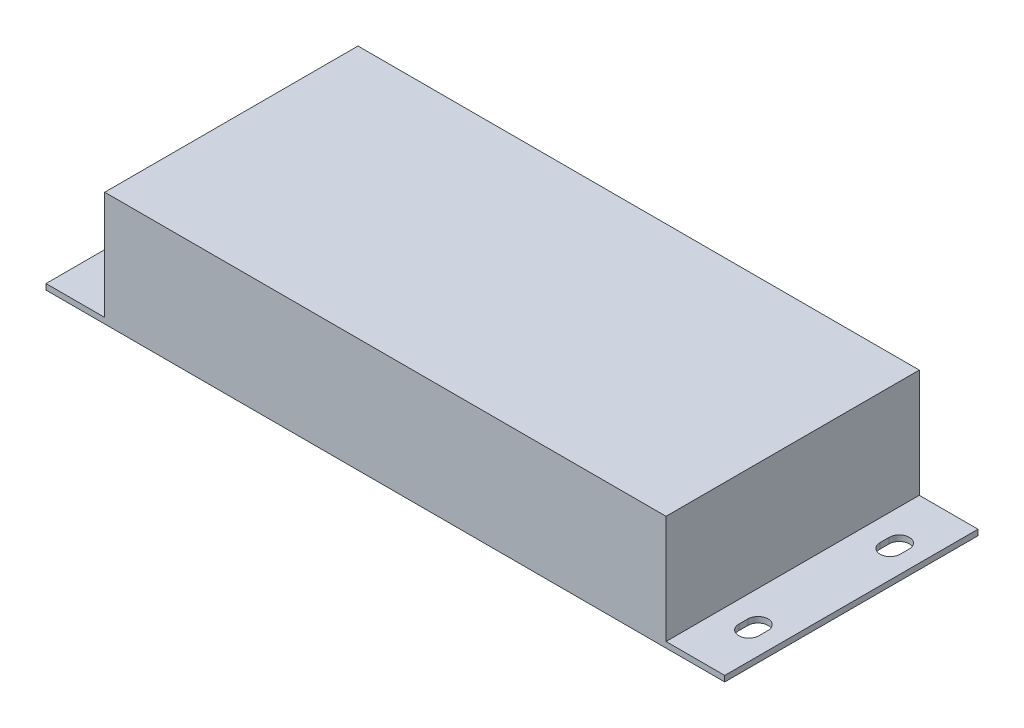
SolidWorks part; units mm, degrees
ref_plane "Front Plane" through (0, 0, 0) normal (0, 0, 1) x (1, 0, 0)
ref_plane "Top Plane" through (0, 0, 0) normal (0, 1, 0) x (1, 0, 0)
ref_plane "Right Plane" through (0, 0, 0) normal (1, 0, 0) x (0, 0, -1)
sketch "Sketch1" plane through (0, 0, 0) normal (0, 1, 0) x (1, 0, 0)
  line L1 (0, 0) -> (99.9236, 0)
  line L2 (0, 0) -> (0, 45.085)
  line L3 (0, 45.085) -> (99.9236, 45.085)
  line L4 (99.9236, 0) -> (99.9236, 45.085)
  dimension "D1" = 99.9236
  dimension "D2" = 45.085
extrude "Boss-Extrude1" add sketch "Sketch1" along normal blind 19.304
sketch "Sketch2" plane through (0, 0, 0) normal (0, -1, 0) x (1, 0, 0)
  line L0 (0, 0) -> (99.9236, -45.085) construction
  line L1 (0, 0) -> (99.9236, 0) construction
  line L2 (-10.4521, -45.085) -> (110.3757, -45.085)
  line L3 (-10.4521, -45.085) -> (-10.4521, 0)
  line L4 (-10.4521, 0) -> (110.3757, 0)
  line L5 (110.3757, -45.085) -> (110.3757, 0)
  line L6 (-10.4521, -45.085) -> (110.3757, 0) construction
  line L7 (-10.4521, 0) -> (110.3757, -45.085) construction
  line L8 (49.9618, 0) -> (49.9618, -45.085) construction
  line L9 (-5.588, -9.1567) -> (-5.588, -10.7823) construction
  line L10 (-3.7973, -9.1567) -> (-3.7973, -10.7823)
  line L11 (-7.3787, -9.1567) -> (-7.3787, -10.7823)
  line L12 (-10.4521, -22.5425) -> (110.3757, -22.5425) construction
  line L13 (-5.588, -35.9283) -> (-5.588, -34.3027) construction
  line L14 (-3.7973, -35.9283) -> (-3.7973, -34.3027)
  line L15 (-7.3787, -35.9283) -> (-7.3787, -34.3027)
  line L16 (105.5116, -9.1567) -> (105.5116, -10.7823) construction
  line L17 (103.7209, -9.1567) -> (103.7209, -10.7823)
  line L18 (107.3023, -9.1567) -> (107.3023, -10.7823)
  line L19 (105.5116, -35.9283) -> (105.5116, -34.3027) construction
  line L20 (103.7209, -35.9283) -> (103.7209, -34.3027)
  line L21 (107.3023, -35.9283) -> (107.3023, -34.3027)
  arc A0 (-3.7973, -9.1567) -> (-7.3787, -9.1567) centre (-5.588, -9.1567) ccw
  arc A1 (-7.3787, -10.7823) -> (-3.7973, -10.7823) centre (-5.588, -10.7823) ccw
  arc A2 (-3.7973, -35.9283) -> (-7.3787, -35.9283) centre (-5.588, -35.9283) cw
  arc A3 (-7.3787, -34.3027) -> (-3.7973, -34.3027) centre (-5.588, -34.3027) cw
  arc A4 (103.7209, -9.1567) -> (107.3023, -9.1567) centre (105.5116, -9.1567) cw
  arc A5 (107.3023, -10.7823) -> (103.7209, -10.7823) centre (105.5116, -10.7823) cw
  arc A6 (103.7209, -35.9283) -> (107.3023, -35.9283) centre (105.5116, -35.9283) ccw
  arc A7 (107.3023, -34.3027) -> (103.7209, -34.3027) centre (105.5116, -34.3027) ccw
  point P4 (49.9618, -22.5425)
  point P15 (-5.588, -9.9695)
  point P24 (-5.588, -35.1155)
  point P31 (105.5116, -9.9695)
  point P38 (105.5116, -35.1155)
  dimension "D1" = 120.8278
  dimension "D2" = 3.5814
  dimension "D3" = 3.0734
  dimension "D4" = 9.1567
  dimension "D5" = 1.6256
extrude "Boss-Extrude2" add sketch "Sketch2" along normal blind 1.016
equation "\"D4@Sketch2\"=0.29in+\"D2@Sketch2\"/2"
equation "\"D5@Sketch2\"=0.205in-\"D2@Sketch2\""
